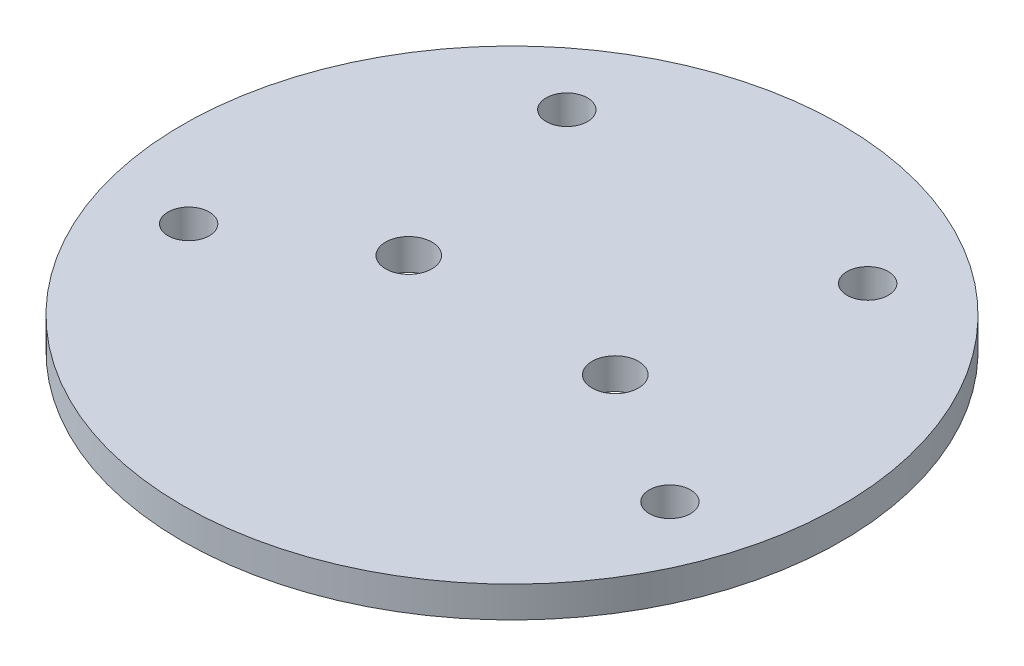
SolidWorks part; units mm, degrees
material "5052-H32"
ref_plane "Front Plane" through (0, 0, 0) normal (0, 0, 1) x (1, 0, 0)
ref_plane "Top Plane" through (0, 0, 0) normal (0, 1, 0) x (1, 0, 0)
ref_plane "Right Plane" through (0, 0, 0) normal (1, 0, 0) x (0, 0, -1)
sketch "Sketch1" plane through (0, 0, 0) normal (0, 1, 0) x (1, 0, 0)
  line L0 (0, 0) -> (-23.1297, 31.5565) construction
  line L1 (0, 0) -> (-41.7254, 0) construction
  line L2 (-37.0005, -12.7186) -> (0, 0) construction
  line L3 (0, -31.6103) -> (0, 47.1695) construction
  circle A0 centre (0, 0) radius 50.673
  circle A3 centre (-15.875, 0) radius 3.5687
  circle A4 centre (15.875, 0) radius 3.5687
  circle A5 centre (-37.0005, -12.7186) radius 3.175
  circle A8 centre (-23.1297, 31.5565) radius 3.175
  circle A9 centre (23.1297, 31.5565) radius 3.175
  circle A10 centre (37.0005, -12.7186) radius 3.175
  dimension "D1" = 101.346
  dimension "D2" = 6.35
  dimension "D3" = 6.35
  dimension "D5" = 15.875
  dimension "D6" = 15.875
  dimension "D4" = 39.1254
  dimension "D7" = 53.76
  dimension "D8" = 39.1254
  dimension "D9" = 18.97
extrude "Boss-Extrude1" add sketch "Sketch1" along normal blind 4.7752
equation "\"allrockets_tube_ID\"= 3.85in"
equation "\"allrockets_tube_OD\"= 4.024in"
equation "\"hole\"= 6.35mm"
equation "\"back_plate_width\"= 28mm"
equation "\"card_spacing\"= 20mm"
equation "\"card_number\"= 6"
equation "\"ToDi\"= 0.05mm"
equation "\"card_diameter\"= 85.86mm"
equation "\"overlap\"= 6.6mm"
equation "\"card_length\"= 68mm"
equation "\"rack_hole_tol\"= 0.35mm"
equation "\"rack_front_width\"= 11.63mm"
equation "\"hole_b_d\"= 39.12541885mm"
equation "\"hole_b_a\"= 18.9721389deg"
equation "\"hole_u_d\"= 39.12541885mm"
equation "\"hole_u_a\"= 53.76090642deg"
equation "\"card_h\"= 61.73mm"
equation "\"sphinx_av\"= 50.292mm"
equation "\"tb_spacing\"= 30mm"
equation "\"D2@Sketch1\"=\"hole\""
equation "\"D4@Sketch1\"=\"hole_u_d\""
equation "\"D7@Sketch1\"=\"hole_u_a\""
equation "\"D8@Sketch1\"=\"hole_b_d\""
equation "\"D9@Sketch1\"=\"hole_b_a\""
